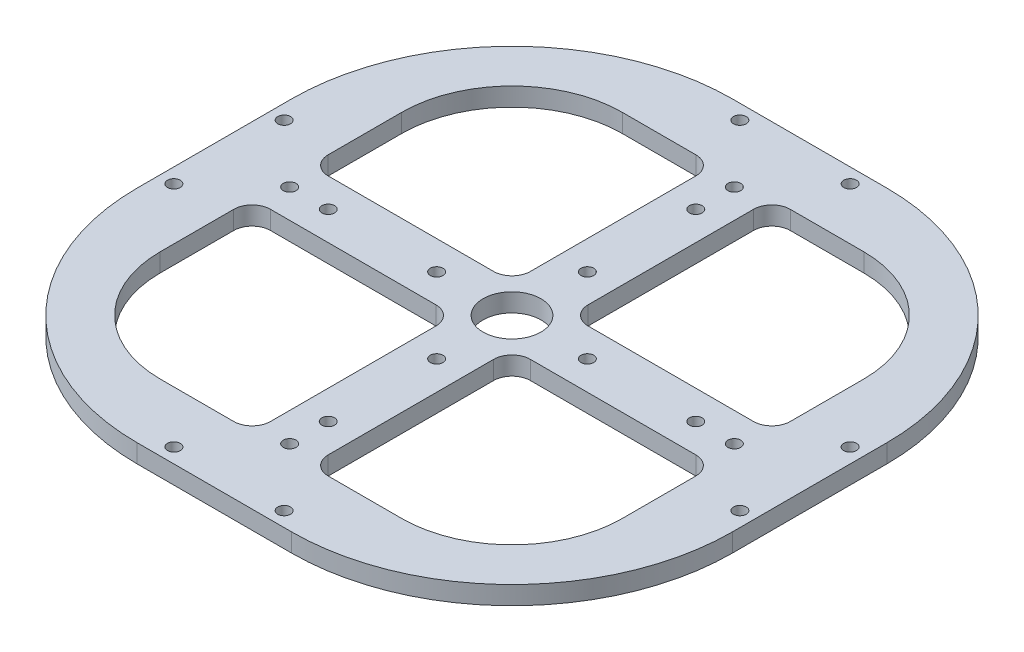
SolidWorks part; units mm, degrees
ref_plane "Front Plane" through (0, 0, 0) normal (0, 0, 1) x (1, 0, 0)
ref_plane "Top Plane" through (0, 0, 0) normal (0, 1, 0) x (1, 0, 0)
ref_plane "Right Plane" through (0, 0, 0) normal (1, 0, 0) x (0, 0, -1)
sketch "Sketch1" plane through (0, 0, 0) normal (0, 1, 0) x (1, 0, 0)
  line L0 (0, 0) -> (63.5, 0) construction
  line L1 (0, 0) -> (76.9579, 0) construction
  line L3 (-102.87, -102.87) -> (102.87, -102.87)
  line L4 (-102.87, -102.87) -> (-102.87, 102.87)
  line L5 (-102.87, 102.87) -> (102.87, 102.87)
  line L6 (102.87, -102.87) -> (102.87, 102.87)
  line L7 (-102.87, -102.87) -> (102.87, 102.87) construction
  line L8 (-102.87, 102.87) -> (102.87, -102.87) construction
  circle A1 centre (63.5, 0) radius 2.2
  circle A2 centre (0, -63.5) radius 2.2
  circle A3 centre (-63.5, 0) radius 2.2
  circle A4 centre (0, 63.5) radius 2.2
  point P14 (0, 0)
  dimension "D3" = 4.4
  dimension "D2" = 63.5
  dimension "D4" = 0
  dimension "D1" = 205.74
extrude "Boss-Extrude1" add sketch "Sketch1" along normal blind 6.35
sketch "Sketch5" plane through (0, 0, 0) normal (0, 0, 1) x (1, 0, 0)
  line L0 (0, 0) -> (0, 41.1667) construction
sketch "Sketch3" plane through (0, 6.35, 0) normal (0, 1, 0) x (1, 0, 0)
  circle A0 centre (0, 0) radius 10
  dimension "D1" = 20
extrude "Cut-Extrude2" cut sketch "Sketch3" against normal through all
sketch "Sketch4" plane through (0, 6.35, 0) normal (0, 1, 0) x (1, 0, 0)
  line L4 (-102.87, 102.87) -> (0, 0) construction
  line L5 (-79.8263, 9.9763) -> (-9.9763, 9.9763)
  line L6 (-79.8263, 9.9763) -> (-79.8263, 79.8263)
  line L7 (-79.8263, 79.8263) -> (-9.9763, 79.8263)
  line L8 (-9.9763, 9.9763) -> (-9.9763, 79.8263)
  line L9 (-79.8263, 9.9763) -> (-9.9763, 79.8263) construction
  line L10 (-79.8263, 79.8263) -> (-9.9763, 9.9763) construction
  point P0 (-44.9013, 44.9013)
  dimension "D1" = 69.85
  dimension "D2" = 63.5
extrude "Cut-Extrude3" cut sketch "Sketch4" against normal through all
fillet "Fillet4" radius 6.35 3 edges at (-9.9763, 3.175, -79.8263) (-9.9763, 3.175, -9.9763) (-79.8263, 3.175, -9.9763)
pattern_circular "CirPattern6" count 4 over 360 about axis through (0, 0, 0) along (0, 1, 0) of "Fillet4", "Cut-Extrude3" reverse direction yes
fillet "Fillet8" radius 38.1 4 edges at (-79.8263, 3.175, 79.8263) (79.8263, 3.175, 79.8263) (79.8263, 3.175, -79.8263) (-79.8263, 3.175, -79.8263)
fillet "Fillet9" radius 76.2 4 edges at (102.87, 3.175, 102.87) (102.87, 3.175, -102.87) (-102.87, 3.175, -102.87) (-102.87, 3.175, 102.87)
sketch "Sketch10" plane through (0, 6.35, 0) normal (0, 1, 0) x (1, 0, 0)
  circle A0 centre (19.05, -97.79) radius 2 construction
  circle A1 centre (-19.05, -97.79) radius 2 construction
  circle A2 centre (0, -76.835) radius 2 construction
  circle A3 centre (0, -26.035) radius 2 construction
  circle A4 centre (19.05, -97.79) radius 2 construction
  circle A5 centre (-19.05, -97.79) radius 2 construction
  circle A6 centre (0, -76.835) radius 2 construction
  circle A7 centre (0, -26.035) radius 2 construction
  circle A8 centre (0, -26.035) radius 2.2
  circle A9 centre (0, -76.835) radius 2.2
  circle A10 centre (-19.05, -97.79) radius 2.2
  circle A11 centre (19.05, -97.79) radius 2.2
  dimension "D1" = 4.4
extrude "Cut-Extrude6" cut sketch "Sketch10" against normal through all
sketch "Sketch11" plane through (0, 0, 0) normal (0, -1, 0) x (1, 0, 0)
  circle A0 centre (-19.05, 97.79) radius 4
  circle A1 centre (19.05, 97.79) radius 4
  circle A2 centre (0, 76.835) radius 4
  circle A3 centre (0, 26.035) radius 4
  dimension "D1" = 8
extrude "Cut-Extrude7" cut sketch "Sketch11" against normal blind 3
pattern_circular "CirPattern4" count 4 over 360 about axis through (0, 0, 0) along (0, 1, 0) of "Cut-Extrude6", "Cut-Extrude7" reverse direction yes
equation "\"D3@Sketch1\"=4.4mm"
equation "\"D1@Sketch3\"=20mm"
equation "\"D1@Sketch10\"=4.4mm"
equation "\"D1@Sketch11\"=8mm"
equation "\"D1@Cut-Extrude7\"=3mm"
